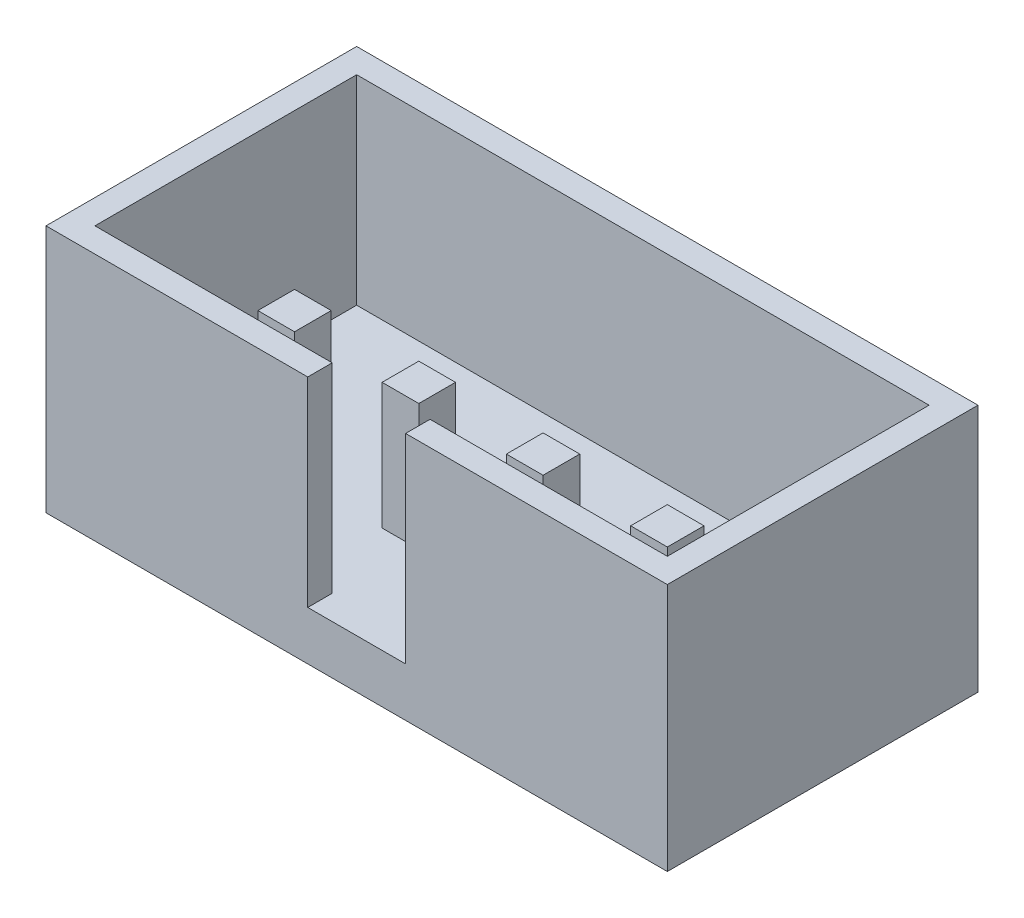
SolidWorks part; units mm, degrees
ref_plane "前视基准面" through (0, 0, 0) normal (0, 0, 1) x (1, 0, 0)
ref_plane "上视基准面" through (0, 0, 0) normal (0, 1, 0) x (1, 0, 0)
ref_plane "右视基准面" through (0, 0, 0) normal (1, 0, 0) x (0, 0, -1)
sketch "草图1" plane through (0, 0, 0) normal (0, 1, 0) x (1, 0, 0)
  line L0 (0, 7.1914) -> (0, -5.4429) construction
  line L1 (-6.35, 3.175) -> (6.35, 3.175)
  line L2 (-6.35, 3.175) -> (-6.35, -3.175)
  line L3 (-6.35, -3.175) -> (6.35, -3.175)
  line L4 (6.35, 3.175) -> (6.35, -3.175)
  line L5 (-10.6234, 0) -> (16.1963, 0) construction
  dimension "D1" = 12.7
  dimension "D2" = 6.35
extrude "拉伸1" add sketch "草图1" along normal blind 5.08
sketch "草图2" plane through (0, 5.08, 0) normal (0, 1, 0) x (-1, 0, 0)
  line L8 (5.85, -2.675) -> (5.85, 2.675)
  line L9 (5.85, 2.675) -> (-5.85, 2.675)
  line L10 (-5.85, 2.675) -> (-5.85, -2.675)
  line L11 (-5.85, -2.675) -> (5.85, -2.675)
  line L12 (5.85, -2.675) -> (5.85, 2.675)
  line L13 (5.85, 2.675) -> (-5.85, 2.675)
  line L14 (-5.85, 2.675) -> (-5.85, -2.675)
  line L15 (-5.85, -2.675) -> (5.85, -2.675)
  dimension "D1" = 0.5
extrude "切除-拉伸1" cut sketch "草图2" against normal offset from surface (4.08 mm away) 1 up to face at (0, 0, 0)
sketch "草图3" plane through (0, 0, 3.175) normal (0, 0, 1) x (1, 0, 0)
  line L0 (-6.35, 5.08) -> (6.35, 5.08) construction
  line L1 (-1, 5.08) -> (1, 5.08)
  line L2 (-1, 5.08) -> (-1, 1)
  line L3 (-1, 1) -> (1, 1)
  line L4 (1, 5.08) -> (1, 1)
  line L5 (5.85, 1) -> (-5.85, 1) construction
  line L6 (0, -1.5083) -> (0, 12.2426) construction
  dimension "D1" = 2
extrude "切除-拉伸2" cut sketch "草图3" against normal blind 1
sketch "草图4" plane through (0, 0, 0) normal (0, -1, 0) x (1, 0, 0)
  line L0 (7.6775, 0.635) -> (-8.5467, 0.635) construction
  line L1 (-6.35, 3.175) -> (6.35, 3.175) construction
  line L2 (0, -3.6953) -> (0, 4.0669) construction
  line L3 (-1.27, 2.1009) -> (-1.27, -0.7012) construction
  line L4 (-1.645, 1.01) -> (-0.895, 1.01)
  line L5 (-1.645, 1.01) -> (-1.645, 0.26)
  line L6 (-1.645, 0.26) -> (-0.895, 0.26)
  line L7 (-0.895, 1.01) -> (-0.895, 0.26)
  line L8 (0.895, 1.01) -> (1.645, 1.01)
  line L9 (0.895, 1.01) -> (0.895, 0.26)
  line L10 (0.895, 0.26) -> (1.645, 0.26)
  line L11 (1.645, 1.01) -> (1.645, 0.26)
  line L12 (3.435, 1.01) -> (4.185, 1.01)
  line L13 (3.435, 1.01) -> (3.435, 0.26)
  line L14 (3.435, 0.26) -> (4.185, 0.26)
  line L15 (4.185, 1.01) -> (4.185, 0.26)
  line L16 (-4.185, 1.01) -> (-3.435, 1.01)
  line L17 (-4.185, 1.01) -> (-4.185, 0.26)
  line L18 (-4.185, 0.26) -> (-3.435, 0.26)
  line L19 (-3.435, 1.01) -> (-3.435, 0.26)
  dimension "D1" = 2.54
  dimension "D2" = 0.75
  dimension "D3" = 0.75
  dimension "D4" = 1.27
extrude "拉伸2" add sketch "草图4" along normal blind 2 and the other way offset from surface 1.5 other way up to face at (0, 5.08, 0.975)
